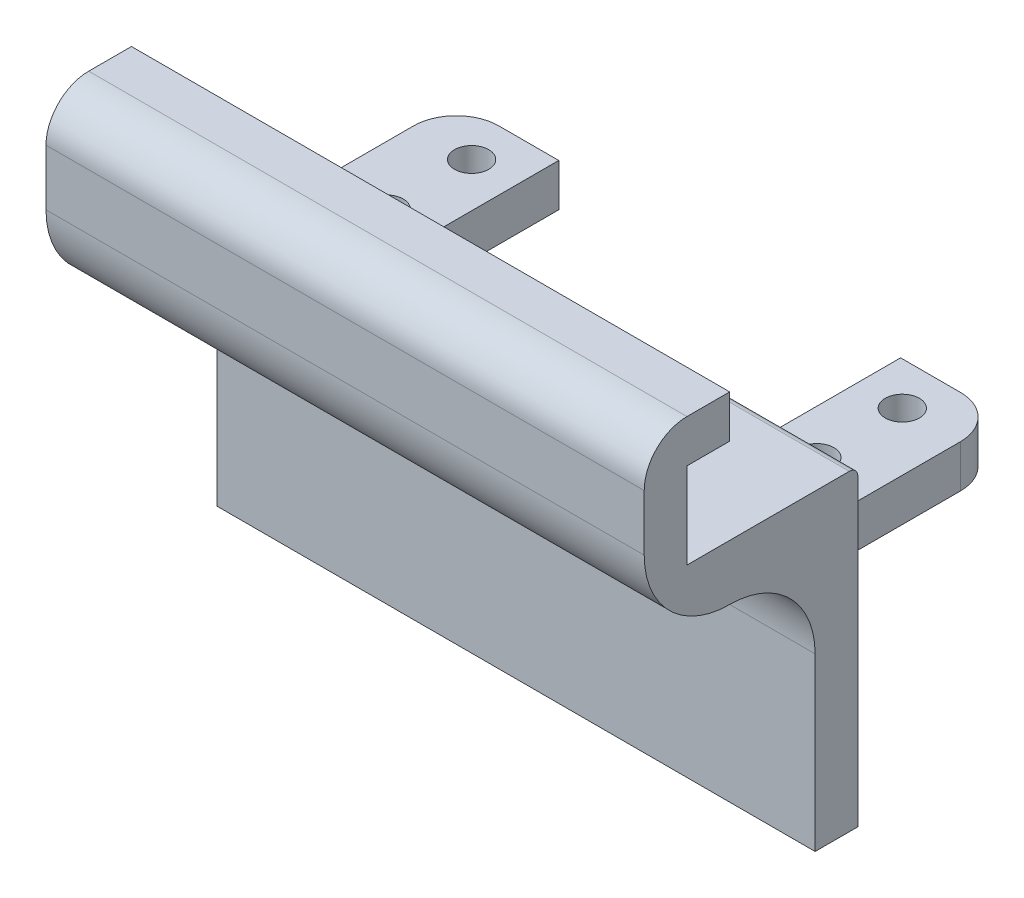
SolidWorks part; units mm, degrees
ref_plane "Plan de face" through (0, 0, 0) normal (0, 0, 1) x (1, 0, 0)
ref_plane "Plan de dessus" through (0, 0, 0) normal (0, 1, 0) x (1, 0, 0)
ref_plane "Plan de droite" through (0, 0, 0) normal (1, 0, 0) x (0, 0, -1)
sketch "Esquisse1" plane through (0, 0, 0) normal (0, 0, 1) x (1, 0, 0)
  line L1 (-35, 15.015) -> (35, 15.015)
  line L2 (-35, 15.015) -> (-35, -15.015)
  line L3 (-35, -15.015) -> (35, -15.015)
  line L4 (35, 15.015) -> (35, -15.015)
  line L5 (-35, 15.015) -> (35, -15.015) construction
  line L6 (-35, -15.015) -> (35, 15.015) construction
  point P0 (0, 0)
  dimension "D1" = 30.03
  dimension "D2" = 70
extrude "Boss.-Extru.1" add sketch "Esquisse1" along normal blind 5
sketch "Esquisse2" plane through (0, 0, 5) normal (0, 0, 1) x (1, 0, 0)
  line L0 (35, 15.015) -> (-35, 15.015) construction
  line L1 (-32, 10.015) -> (-20, 10.015)
  line L2 (-32, 10.015) -> (-32, 15.015)
  line L3 (-32, 15.015) -> (-20, 15.015)
  line L4 (-20, 10.015) -> (-20, 15.015)
  line L5 (-32, 10.015) -> (-20, 15.015) construction
  line L6 (-32, 15.015) -> (-20, 10.015) construction
  line L7 (-35, 15.015) -> (-35, -15.015) construction
  line L8 (0, 23.7713) -> (0, -21.1965) construction
  line L9 (32, 15.015) -> (20, 15.015)
  line L10 (20, 10.015) -> (20, 15.015)
  line L11 (32, 10.015) -> (20, 10.015)
  line L12 (32, 10.015) -> (32, 15.015)
  point P0 (-26, 12.515)
  dimension "D1" = 9
  dimension "D2" = 5
  dimension "D3" = 12
extrude "Boss.-Extru.2" add sketch "Esquisse2" against normal blind 20 from offset 5 offset against normal yes
fillet "Congé1" radius 3 1 edges at (32, 12.515, 0) type face fillet first side face at (32, 12.515, -10) second side face at (0, 8.3433, 0)
fillet "Congé2" radius 3 1 edges at (-32, 12.515, 0) type face fillet first side face at (-32, 12.515, -10) second side face at (-6.4, 7.009, 0)
fillet "Congé12" radius 5 1 edges at (-20, 12.515, 0) type face fillet first side face at (-20, 12.515, -10) second side face at (0, 5.0075, 0)
fillet "Congé11" radius 5 1 edges at (20, 12.515, 0) type face fillet first side face at (20, 12.515, -10) second side face at (1.25, 5.0075, 0)
sketch "Esquisse6" plane through (35, 0, 0) normal (1, 0, 0) x (0, 0, -1)
  line L0 (-5, 15.015) -> (-25, 15.015)
  line L1 (-25, 15.015) -> (-25, 36.565)
  line L2 (-25, 36.565) -> (-20, 36.565)
  line L3 (-20, 36.565) -> (-20, 21.515)
  line L4 (-20, 21.515) -> (-5, 21.515)
  line L6 (-5, 15.015) -> (0, 15.015)
  line L7 (0, 15.015) -> (0, 21.515)
  line L8 (0, 21.515) -> (-5, 21.515)
  dimension "D1" = 21.55
  dimension "D2" = 20
  dimension "D3" = 6.5
  dimension "D4" = 5
extrude "Boss.-Extru.5" add sketch "Esquisse6" against normal through all
fillet "Congé13" radius 10 1 edges at (0, 15.015, 25)
fillet "Congé14" radius 5 1 edges at (0, 36.565, 25)
sketch "Esquisse7" plane through (0, 0, 20) normal (0, 0, -1) x (-1, 0, 0)
  line L0 (-35, 31.565) -> (35, 31.565)
  line L4 (-35, 36.565) -> (-35, 21.515)
  line L5 (-35, 21.515) -> (35, 21.515)
  line L6 (35, 21.515) -> (35, 36.565)
  line L7 (35, 36.565) -> (-35, 36.565)
  line L8 (-35, 36.565) -> (-35, 31.565)
  line L10 (35, 31.565) -> (35, 36.565)
  line L13 (35, 36.565) -> (-35, 36.565)
  dimension "D1" = 0
extrude "Boss.-Extru.6" add sketch "Esquisse7" along normal blind 5
fillet "Congé15" radius 10 1 edges at (0, 15.015, 5) type face fillet first side face at (0, 0, 5) second side face at (0, 15.015, 10)
fillet "Congé16" radius 1 1 edges at (0, 21.515, 0)
sketch "Esquisse8" plane through (32, 0, 0) normal (1, 0, 0) x (0, 0, -1)
  line L2 (0, 15.0097) -> (1, 15.015)
  line L4 (0, 15.0097) -> (0, 20.515)
  line L7 (3, 15.015) -> (0, 15.015) construction
  line L8 (1, 15.015) -> (0, 20.515)
  dimension "D1" = 1
  dimension "D2" = 80
extrude "Boss.-Extru.7" add sketch "Esquisse8" against normal blind 2 from offset 2 contours L8 L4 L2 region at (32, 16.8466, -0.3333) offset against normal yes
sketch "Esquisse9" plane through (28, 0, 0) normal (-1, 0, 0) x (0, 0, 1)
  line L3 (0, 20.515) -> (-1, 15.015)
  line L4 (-1, 15.015) -> (0, 15.015)
  line L5 (0, 15.015) -> (0, 20.515)
  line L6 (0, 20.515) -> (-1, 15.015)
  line L7 (-1, 15.015) -> (0, 15.015)
  line L8 (0, 15.015) -> (0, 20.515)
  dimension "D1" = 0
extrude "Boss.-Extru.8" add sketch "Esquisse9" along normal blind 2 from offset 4
mirror "Symétrie3" about plane through (0, 0, 0) normal (1, 0, 0) of "Boss.-Extru.7", "Boss.-Extru.8"
sketch "Esquisse11" plane through (0, 10.015, 0) normal (0, -1, 0) x (1, 0, 0)
  circle A0 centre (25.2, -15) radius 2
  circle A1 centre (25.2, -5) radius 2
  circle A2 centre (-25.2, -15) radius 2
  circle A3 centre (-25.2, -5) radius 2
extrude "Enlèv. mat.-Extru.1" cut sketch "Esquisse11" against normal through all
fillet "Congé17" radius 5 2 edges at (-32, 12.515, -20) (32, 12.515, -20)
